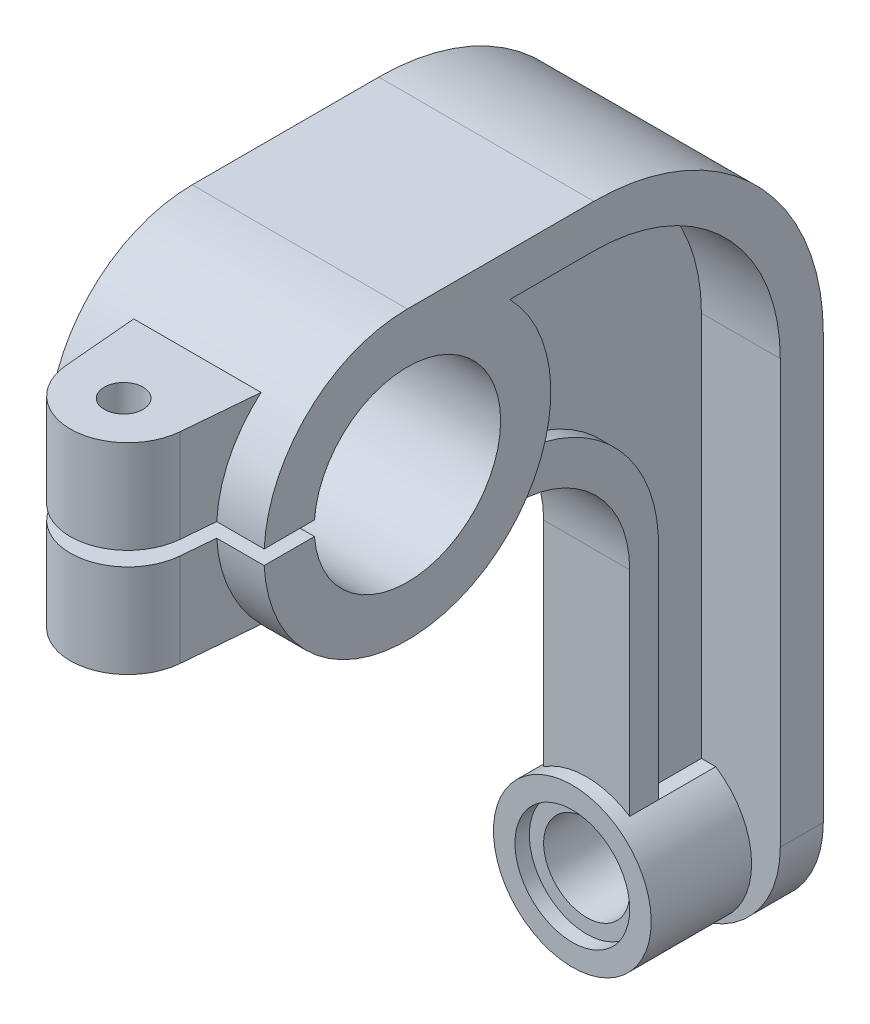
SolidWorks part; units mm, degrees
ref_plane "Front Plane" through (0, 0, 0) normal (1, 0, 0) x (0, 1, 0)
ref_plane "Top Plane" through (0, 0, 0) normal (0, 0, 1) x (0, 1, 0)
ref_plane "Right Plane" through (0, 0, 0) normal (0, 1, 0) x (-1, 0, 0)
sketch "Sketch1" plane through (0, 0, 0) normal (1, 0, 0) x (0, 1, 0)
  line L0 (162.3087, -25) -> (-102.6913, -25)
  line L1 (62.3087, 120) -> (62.3087, 25)
  line L2 (162.3087, 120) -> (162.3087, -25)
  line L3 (62.3087, 25) -> (-102.6913, 25)
  line L4 (-102.6913, 25) -> (-102.6913, -25)
  arc A0 (162.3087, 120) -> (62.3087, 120) centre (112.3087, 120) ccw
  circle A1 centre (112.3087, 120) radius 32.5
  dimension "D3" = 100
  dimension "D5" = 65
  dimension "D1" = 265
  dimension "D2" = 25
  dimension "D4" = 25
extrude "Boss-Extrude1" add sketch "Sketch1" along normal blind 75
fillet "Fillet1" radius 80 1 edges at (37.5, 162.3087, -25)
sketch "Sketch3" plane through (0, 0, 25) normal (0, 0, 1) x (1, 0, 0)
  line L1 (0, 62.3087) -> (0, -102.6913) construction
  line L2 (22.5, 62.3087) -> (22.5, -52.1425)
  line L3 (75, 62.3087) -> (0, 62.3087) construction
  line L4 (52.5, -52.1425) -> (52.5, 62.3087)
  line L5 (52.5, 62.3087) -> (22.5, 62.3087)
  line L6 (75, 62.3087) -> (75, -102.6913) construction
  line L7 (75, -102.6913) -> (0, -102.6913) construction
  circle A0 centre (37.5, -75.1913) radius 27.5
  line M3 (0, 62.3087) -> (0, -102.6913)
  line M4 (0, -102.6913) -> (75, -102.6913)
  line M5 (75, -102.6913) -> (75, 62.3087)
  line M6 (75, 62.3087) -> (0, 62.3087)
  dimension "D1" = 55
  dimension "D2" = 22.5
  dimension "D3" = 37.5
  dimension "D4" = 22.5
  dimension "D5" = 27.5
extrude "Cut-Extrude3" cut sketch "Sketch3" against normal blind 35 contours A0 L4 M4 M5 M6 | A0 L2 M6 M3 M4 region at (10.5979, -14.0078, 25) region at (64.4021, -14.0078, 25)
fillet "Fillet2" radius 37.5 2 edges at (0, -102.6913, -17.5) (75, -102.6913, -17.5)
sketch "Sketch7" plane through (0, 0, 25) normal (0, 0, 1) x (1, 0, 0)
  line L14 (22.5, 62.3087) -> (22.5, -52.1425)
  line L15 (52.5, -52.1425) -> (52.5, 62.3087)
  line L16 (52.5, 62.3087) -> (22.5, 62.3087)
  line L17 (22.5, 62.3087) -> (22.5, -52.1425)
  line L18 (52.5, -52.1425) -> (52.5, 62.3087)
  line L19 (52.5, 62.3087) -> (22.5, 62.3087)
  circle A3 centre (37.5, -75.1913) radius 27.5
  arc A4 (22.5, -52.1425) -> (52.5, -52.1425) centre (37.5, -75.1913) ccw
  arc A5 (22.5, -52.1425) -> (52.5, -52.1425) centre (37.5, -75.1913) ccw
  line M1 (52.5, -52.1425) -> (52.5, 62.3087)
  line M3 (22.5, 62.3087) -> (22.5, -52.1425)
  line M20 (52.5, 62.3087) -> (22.5, 62.3087)
  dimension "D1" = 0
extrude "Cut-Extrude13" cut sketch "Sketch7" against normal blind 5 contours A3 M1 M20 M3 region at (37.5, 6.5849, 25)
fillet "Fillet6" radius 40 1 edges at (37.5, 62.3087, 20)
sketch "Sketch5" plane through (75, 0, 0) normal (1, 0, 0) x (0, 1, 0)
  line L0 (62.3087, 120) -> (162.3087, 120) construction
  line L1 (-52.1425, 10) -> (22.3087, 10)
  line L2 (-52.1425, -10) -> (-52.1425, 20) construction
  line L3 (62.3087, 25) -> (-52.1425, 25) construction
  line L4 (77.3087, 84.2929) -> (77.3087, 60)
  line L5 (147.3087, 84.2929) -> (147.3087, 55)
  line L6 (162.3087, 55) -> (162.3087, 120) construction
  line L8 (82.3087, -25) -> (-65.1913, -25)
  line L9 (82.3087, -25) -> (-65.1913, -25)
  line L10 (-65.1913, -25) -> (-102.6913, -25)
  line L11 (-65.1913, -25) -> (-102.6913, -25)
  line L12 (-102.6913, -25) -> (-102.6913, -10)
  line L13 (-102.6913, -25) -> (-102.6913, -10)
  line L14 (-47.6913, 25) -> (-47.6913, 20)
  line L15 (-47.6913, 25) -> (-47.6913, 20)
  line L16 (-102.6913, 25) -> (-47.6913, 25)
  line L17 (-102.6913, 25) -> (-47.6913, 25)
  line L18 (-47.6913, 20) -> (22.3087, 20)
  line L20 (62.3087, 60) -> (62.3087, 120)
  line L21 (62.3087, 60) -> (62.3087, 120)
  line L22 (162.3087, 120) -> (162.3087, 55)
  line L23 (162.3087, 120) -> (162.3087, 55)
  line L24 (-52.1425, 10) -> (-52.1425, -10)
  line L25 (-52.1425, -10) -> (82.3087, -10)
  line L26 (-65.1913, -10) -> (62.3087, -10) construction
  line L27 (62.3087, 120) -> (62.3087, 25)
  line L28 (-102.6913, -10) -> (-47.6913, 20)
  line L29 (62.3087, -10) -> (62.3087, 60) construction
  line L30 (-47.6913, 20) -> (22.3087, 20)
  line L36 (-102.6913, -10) -> (-47.6913, 20)
  circle A0 centre (112.3087, 120) radius 50
  arc A1 (22.3087, 20) -> (62.3087, 60) centre (22.3087, 60) ccw
  arc A3 (162.3087, 120) -> (62.3087, 120) centre (112.3087, 120) ccw
  arc A4 (162.3087, 120) -> (62.3087, 120) centre (112.3087, 120) ccw
  arc A5 (82.3087, -25) -> (162.3087, 55) centre (82.3087, 55) ccw
  arc A6 (82.3087, -25) -> (162.3087, 55) centre (82.3087, 55) ccw
  arc A7 (77.3087, 60) -> (22.3087, 10) centre (24.8087, 62.5) cw
  arc A8 (82.3087, -10) -> (147.3087, 55) centre (82.3087, 55) ccw
  arc A10 (22.3087, 20) -> (62.3087, 60) centre (22.3087, 60) ccw
  line M4 (62.3087, -10) -> (-65.1913, -10)
  line M10 (62.3087, 120) -> (62.3087, -10)
  dimension "D1" = 100
  dimension "D5" = 52.5595
  dimension "D2" = 15
  dimension "D3" = 15
  dimension "D4" = 15
extrude "Cut-Extrude14" cut sketch "Sketch5" against normal blind 27.5 contours L25 A8 L5 A0 L4 A7 L27 M10 | L27 A7 L1 L24 M4 M10 region at (75, 8.6182, 1.0664) region at (75, 103.898, 34.5136)
sketch "Sketch8" plane through (75, 0, 0) normal (1, 0, 0) x (0, 1, 0)
  line L7 (82.3087, -10) -> (-65.1913, -10)
  line L8 (-65.1913, -10) -> (-65.1913, -25)
  line L9 (-65.1913, -25) -> (82.3087, -25)
  line L10 (162.3087, 55) -> (162.3087, 120)
  line L11 (62.3087, 120) -> (62.3087, 25.6727)
  line L12 (77.3087, 60) -> (77.3087, 84.2929)
  line L13 (147.3087, 84.2929) -> (147.3087, 55)
  line L14 (82.3087, -10) -> (-65.1913, -10)
  line L15 (-65.1913, -10) -> (-65.1913, -25)
  line L16 (-65.1913, -25) -> (82.3087, -25)
  line L17 (162.3087, 55) -> (162.3087, 120)
  line L18 (62.3087, 120) -> (62.3087, 25.6727)
  line L19 (77.3087, 60) -> (77.3087, 84.2929)
  line L20 (147.3087, 84.2929) -> (147.3087, 55)
  arc A0 (62.3087, 120) -> (77.3087, 84.2929) centre (112.3087, 120) ccw
  arc A5 (82.3087, -10) -> (147.3087, 55) centre (82.3087, 55) ccw
  arc A6 (82.3087, -25) -> (162.3087, 55) centre (82.3087, 55) ccw
  arc A7 (162.3087, 120) -> (62.3087, 120) centre (112.3087, 120) ccw
  arc A8 (62.3087, 25.6727) -> (77.3087, 60) centre (24.8087, 62.5) ccw
  arc A9 (77.3087, 84.2929) -> (147.3087, 84.2929) centre (112.3087, 120) ccw
  arc A10 (82.3087, -10) -> (147.3087, 55) centre (82.3087, 55) ccw
  arc A11 (82.3087, -25) -> (162.3087, 55) centre (82.3087, 55) ccw
  arc A12 (162.3087, 120) -> (62.3087, 120) centre (112.3087, 120) ccw
  arc A13 (62.3087, 25.6727) -> (77.3087, 60) centre (24.8087, 62.5) ccw
  arc A14 (77.3087, 84.2929) -> (147.3087, 84.2929) centre (112.3087, 120) ccw
  line M20 (62.3087, 120) -> (62.3087, 25.6727)
  arc M21 (62.3087, 25.6727) -> (77.3087, 60) centre (24.8087, 62.5) ccw
  line M22 (77.3087, 60) -> (77.3087, 84.2929)
  dimension "D1" = 0
extrude "Cut-Extrude15" cut sketch "Sketch8" against normal blind 22.5 contours A0 M20 M21 M22 region at (75, 68.6011, 66.1918)
ref_plane "Plane1" through (37.5, 0, 0) normal (1, 0, 0) x (0, 1, 0)
mirror "Mirror2" about plane through (37.5, 0, 0) normal (1, 0, 0) of "Cut-Extrude15", "Cut-Extrude14"
sketch "Sketch9" plane through (0, 0, 25) normal (0, 0, 1) x (1, 0, 0)
  line L0 (10, -75.1913) -> (65, -75.1913) construction
  circle A0 centre (37.5, -75.1913) radius 27.5 construction
  circle A2 centre (37.5, -75.1913) radius 15
  arc A3 (52.5, -52.1425) -> (22.5, -52.1425) centre (37.5, -75.1913) ccw construction
  arc A4 (52.5, -52.1425) -> (22.5, -52.1425) centre (37.5, -75.1913) ccw
  circle A6 centre (37.5, -75.1913) radius 27.5
  circle A7 centre (37.5, -75.1913) radius 27.5
  dimension "D2" = 30
  dimension "D3" = 0
extrude "Cut-Extrude16" cut sketch "Sketch9" against normal through all contours A2
sketch "Sketch10" plane through (0, 0, 25) normal (0, 0, 1) x (1, 0, 0)
  line L0 (10, -75.1913) -> (37.5, -75.1913) construction
  circle A0 centre (37.5, -75.1913) radius 27.5 construction
  arc A1 (22.5, -52.1425) -> (37.5, -102.6913) centre (37.5, -75.1913) ccw construction
  circle A2 centre (37.5, -75.1913) radius 20
  dimension "D1" = 40
extrude "Cut-Extrude17" cut sketch "Sketch10" against normal blind 5
mirror "Mirror3" about plane through (0, 0, 0) normal (0, 0, 1) of "Cut-Extrude17", "Cut-Extrude16"
ref_plane "Plane10" through (0, 77.3087, 0) normal (0, 1, 0) x (-1, 0, 0)
sketch "Sketch13" plane through (0, 77.3087, 0) normal (0, 1, 0) x (-1, 0, 0)
  line L0 (0, -25) -> (-75, -25) construction
  line L1 (-57.4239, 181.7431) -> (-59.933, 153.0641)
  line L2 (-17.5761, 181.7431) -> (-15.067, 153.0641)
  line L4 (-37.5, -25) -> (-37.5, 180) construction
  line L5 (-59.933, 153.0641) -> (-15.067, 153.0641)
  arc A0 (-17.5761, 181.7431) -> (-57.4239, 181.7431) centre (-37.5, 180) ccw
  dimension "D2" = 40
  dimension "D1" = 205
  dimension "D3" = 10
  dimension "D4" = 85
extrude "Boss-Extrude2" add sketch "Sketch13" along normal blind 70
hole_wizard "CBORE for M14 Hex Head Cap Screw1" positions "Sketch19" profile "Sketch20" counterbore size "M14" standard "ANSI Metric" end condition through all
sketch "Sketch19" plane through (0, 77.3087, 0) normal (0, -1, 0) x (-1, 0, 0)
  point P0 (-37.5, -181.4159)
sketch "Sketch20" plane through (37.5, 77.3087, 181.4159) normal (1, 0, 0) x (0, 0, -1)
  line L0 (0, 0) -> (0, 85)
  line L1 (0, 85) -> (6.75, 85)
  line L3 (6.75, 85) -> (6.75, 6.6)
  line L4 (11, 6.6) -> (6.75, 6.6)
  line L5 (11, 6.6) -> (11, 2.2236)
  line L6 (11, 2.2236) -> (13.65, 0)
  line L7 (13.65, 0) -> (0, 0)
  line L8 (-11, 2.2236) -> (-13.65, 0) construction
  line L11 (0, -6.35) -> (0, 107.95) construction
  dimension "Thru Hole Dia." = 13.5
  dimension "Thru Hole Depth" = 85
  dimension "C'Bore Dia." = 22
  dimension "C'Bore Depth" = 6.6
  dimension "Near C'Sink Dia." = 27.3
  dimension "Near C'Sink Angle" = 100
ref_plane "Plane12" through (0, 0, 200) normal (0, 0, -1) x (-1, 0, 0)
sketch "Sketch18" plane through (0, 0, 200) normal (0, 0, -1) x (-1, 0, 0)
  line L17 (-75, 162.3087) -> (0, 162.3087) construction
  line L61 (-75, 162.3087) -> (0, 162.3087)
  line L62 (0, 112.3087) -> (-75, 112.3087) construction
  line L63 (0, 114.8087) -> (-75, 114.8087)
  line L64 (-75, 114.8087) -> (-75, 109.8087)
  line L65 (-75, 109.8087) -> (0, 109.8087)
  line L66 (0, 109.8087) -> (0, 114.8087)
  dimension "D2" = 2.5
  dimension "D3" = 2.5
  dimension "D1" = 47.5
extrude "Cut-Extrude20" cut sketch "Sketch18" along normal up to surface (47.5963 mm away) contours L65 L66 L63 L64 up to face at (75, 112.3087, 87.5)
